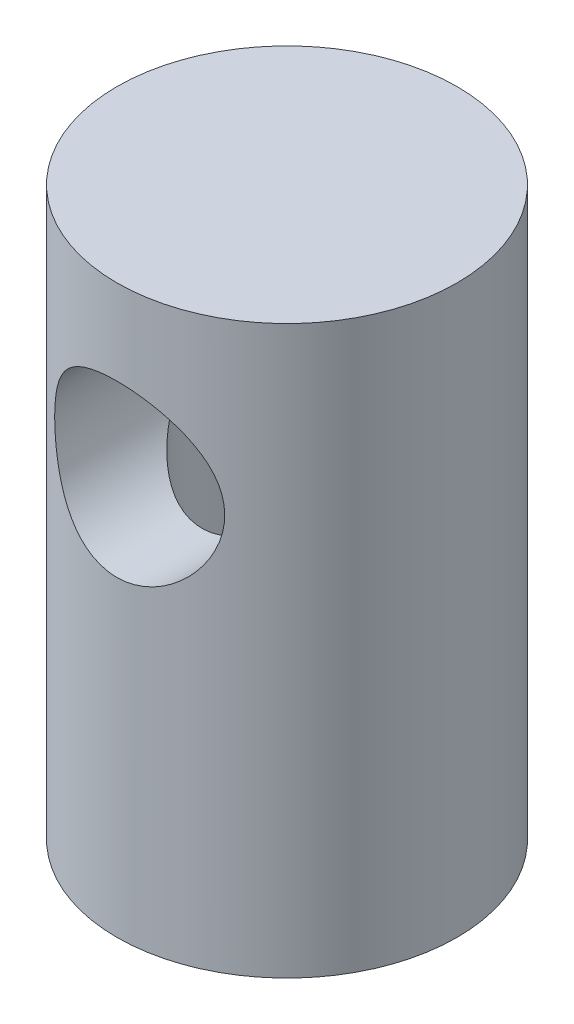
SolidWorks part; units mm, degrees
ref_plane "Front Plane" through (0, 0, 0) normal (0, 0, 1) x (1, 0, 0)
ref_plane "Top Plane" through (0, 0, 0) normal (0, 1, 0) x (1, 0, 0)
ref_plane "Right Plane" through (0, 0, 0) normal (1, 0, 0) x (0, 0, -1)
sketch "Sketch1" plane through (0, 0, 0) normal (0, 1, 0) x (1, 0, 0)
  circle A0 centre (0, 0) radius 3.81
  dimension "D1" = 7.62
extrude "Boss-Extrude1" add sketch "Sketch1" along normal blind 12.7 contours A0
sketch "Sketch2" plane through (0, 0, 0) normal (0, 0, 1) x (1, 0, 0)
  line L0 (3.81, 12.7) -> (-3.81, 12.7) construction
  circle A0 centre (0, 8.89) radius 1.905
  point P0 (0, 9.8348)
  dimension "D1" = 3.81
  dimension "D2" = 3.81
extrude "Cut-Extrude1" cut sketch "Sketch2" against normal up to surface and the other way blind 19.05 up to face at (0, 12.7, 3.81)
sketch "Sketch3" plane through (0, 0, 0) normal (0, -1, 0) x (1, 0, 0)
  circle A0 centre (0, 0) radius 1.905
  dimension "D1" = 3.81
extrude "Cut-Extrude2" cut sketch "Sketch3" against normal up to surface (6.985 mm away) up to face at (-1.8941, 9.0934, -3.3058)
